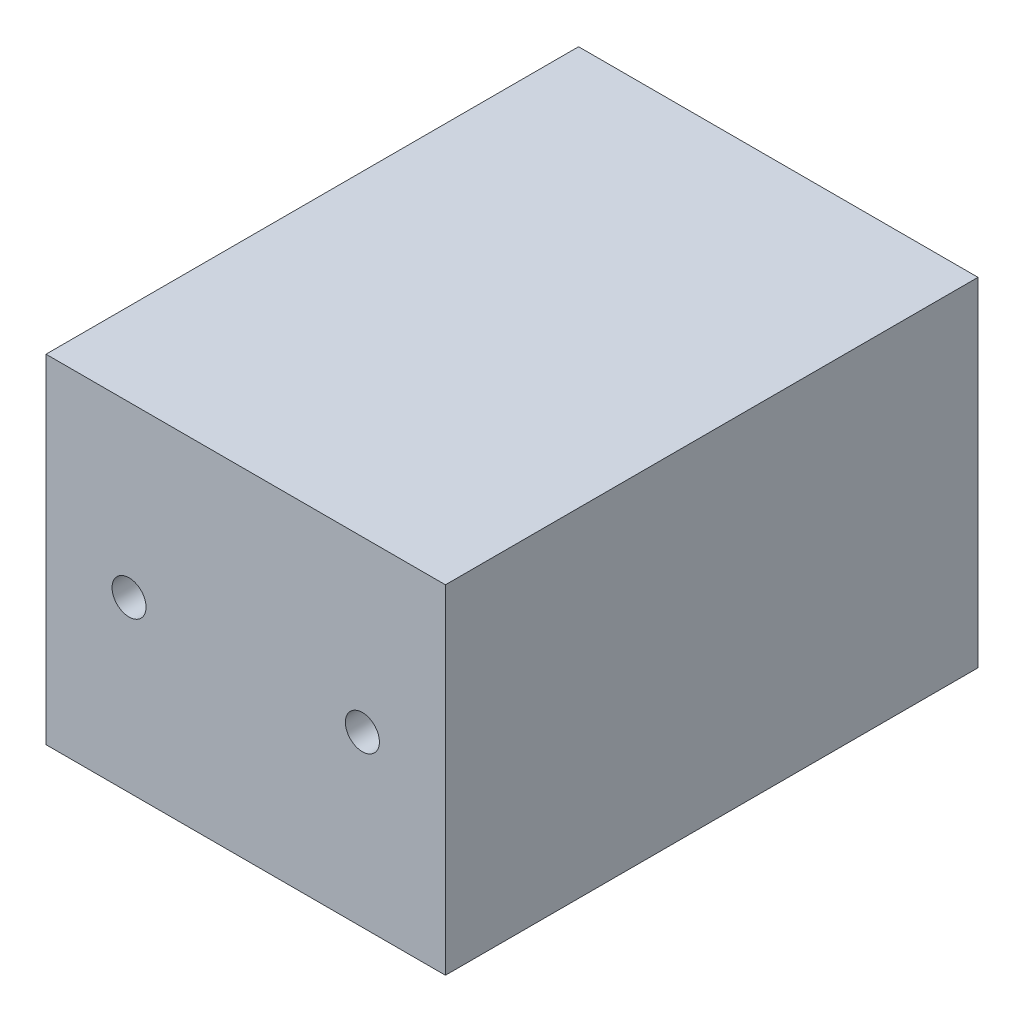
SolidWorks part; units mm, degrees
material "6061 Alloy"
ref_plane "Front Plane" through (0, 0, 0) normal (0, 0, 1) x (1, 0, 0)
ref_plane "Top Plane" through (0, 0, 0) normal (0, 1, 0) x (1, 0, 0)
ref_plane "Right Plane" through (0, 0, 0) normal (1, 0, 0) x (0, 0, -1)
sketch "Sketch1" plane through (0, 0, 0) normal (0, 1, 0) x (1, 0, 0)
  line L1 (0, 0) -> (60, 0)
  line L2 (0, 0) -> (0, 80)
  line L3 (0, 80) -> (60, 80)
  line L4 (60, 0) -> (60, 80)
  dimension "D1" = 80
  dimension "D2" = 60
extrude "Boss-Extrude1" add sketch "Sketch1" along normal blind 50.8
sketch "Sketch2" plane through (0, 0, 0) normal (0, 0, 1) x (1, 0, 0)
  line L0 (0, 25.4) -> (60, 25.4) construction
  line L1 (0, 50.8) -> (0, 0) construction
  line L2 (60, 50.8) -> (60, 0) construction
  line L3 (30, 50.8) -> (30, 0) construction
  line L4 (0, 50.8) -> (60, 50.8) construction
  line L5 (0, 0) -> (60, 0) construction
  point P12 (12.474, 25.4)
  point P13 (47.526, 25.4)
  dimension "D1" = 17.526
  dimension "D2" = 17.526
hole_wizard "1/4-20 Tapped Hole1" positions "3DSketch2" profile "Sketch4" tap size "1/4-20" standard "ANSI Inch" end condition through all
sketch3d "3DSketch2"
  point P0 (12.474, 25.4, 0)
  point P3 (47.526, 25.4, 0)
sketch "Sketch4" plane through (12.474, 25.4, 0) normal (1, 0, 0) x (0, -1, 0)
  line L0 (0, 0) -> (0, 80)
  line L1 (0, 80) -> (2.5527, 80)
  line L2 (2.5527, 80) -> (2.5527, 0)
  line L5 (2.5527, 0) -> (0, 0)
  line L11 (0, -6.35) -> (0, 107.95) construction
  dimension "Thru Tap Drill Dia." = 5.1054
  dimension "Thru Tap Drill Depth" = 80
cosmetic thread "Hole Thread1" parameters "D2"=6.35
cosmetic thread "Hole Thread2" parameters "D2"=6.35
